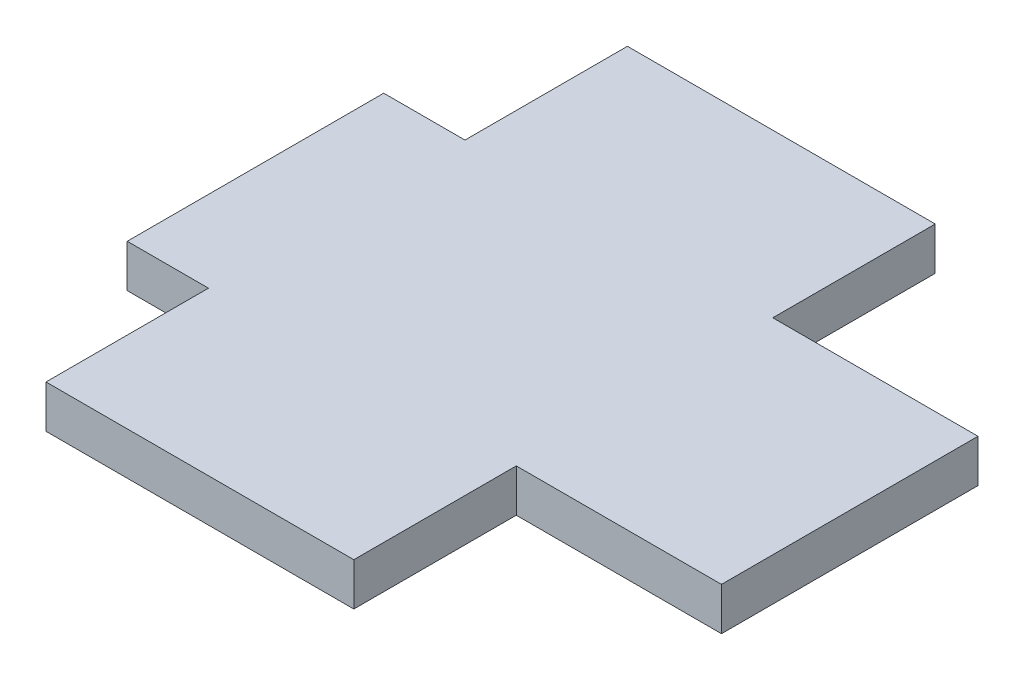
SolidWorks part; units mm, degrees
ref_plane "Front" through (0, 0, 0) normal (0, 0, 1) x (1, 0, 0)
ref_plane "Top" through (0, 0, 0) normal (0, 1, 0) x (1, 0, 0)
ref_plane "Right" through (0, 0, 0) normal (1, 0, 0) x (0, 0, -1)
sketch "Sketch1" plane through (0, 0, 0) normal (0, 1, 0) x (1, 0, 0)
  line L0 (11.43, 43.18) -> (11.43, 0) construction
  line L1 (0, 0) -> (22.86, 0)
  line L2 (0, 0) -> (0, 12.065)
  line L3 (0, 43.18) -> (22.86, 43.18)
  line L4 (22.86, 0) -> (22.86, 12.065)
  line L5 (0, 12.065) -> (-6.0325, 12.065)
  line L7 (0, 31.115) -> (-6.0325, 31.115)
  line L8 (-6.0325, 12.065) -> (-6.0325, 31.115)
  line L9 (0, 31.115) -> (0, 43.18)
  line L10 (22.86, 31.115) -> (22.86, 43.18)
  line L11 (22.86, 12.065) -> (38.1, 12.065)
  line L13 (22.86, 31.115) -> (38.1, 31.115)
  line L14 (38.1, 12.065) -> (38.1, 31.115)
  point P11 (-6.0325, 21.59)
  point P12 (11.43, 21.59)
  dimension "D1" = 22.86
  dimension "D2" = 43.18
  dimension "D3" = 19.05
  dimension "D4" = 6.0325
  dimension "D5" = 15.24
extrude "Boss-Extrude1" add sketch "Sketch1" along normal blind 3.175
